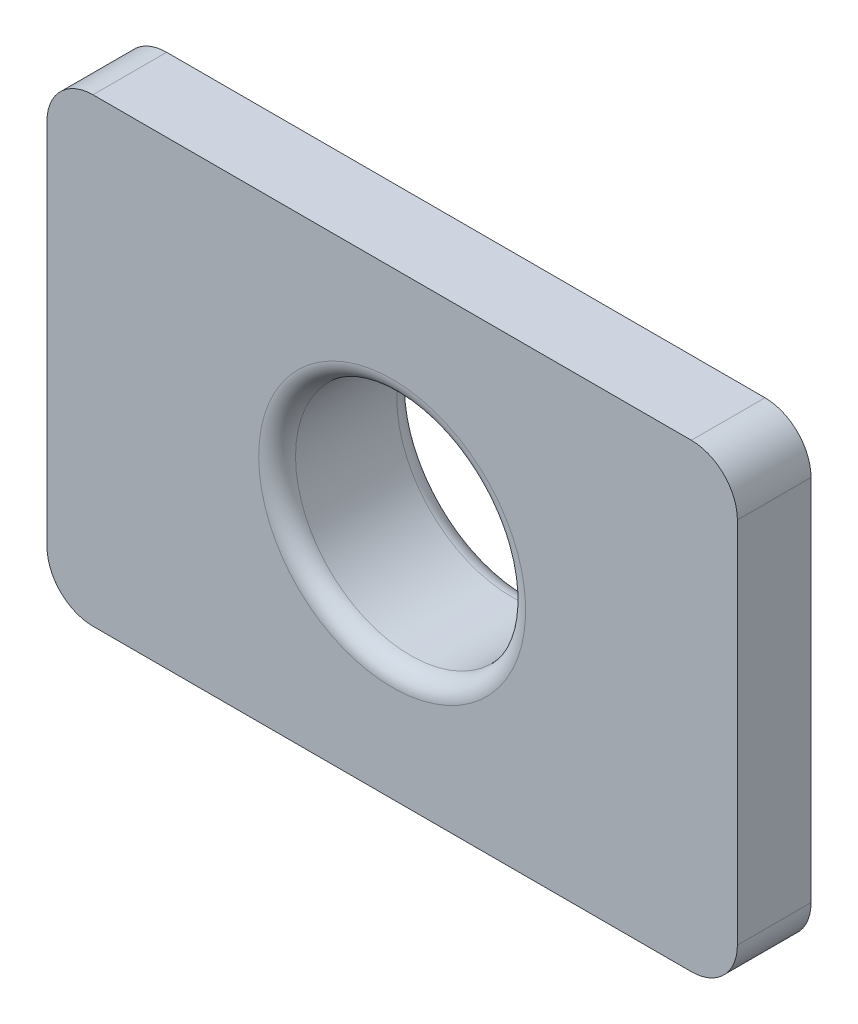
SolidWorks part; units mm, degrees
ref_plane "Front Plane" through (0, 0, 0) normal (0, 0, 1) x (1, 0, 0)
ref_plane "Top Plane" through (0, 0, 0) normal (0, 1, 0) x (1, 0, 0)
ref_plane "Right Plane" through (0, 0, 0) normal (1, 0, 0) x (0, 0, -1)
sketch "Sketch1" plane through (0, 0, 0) normal (0, 0, 1) x (1, 0, 0)
  line L0 (0, 5) -> (15, 5) construction
  line L1 (0, 0) -> (15, 0)
  line L2 (0, 0) -> (0, 10)
  line L3 (0, 10) -> (15, 10)
  line L4 (15, 0) -> (15, 10)
  circle A0 centre (7.5, 5) radius 2.5
  dimension "D3" = 5
  dimension "D1" = 15
  dimension "D2" = 10
extrude "Boss-Extrude1" add sketch "Sketch1" along normal blind 1.6
sketch "Sketch2" plane through (0, 0, 0) normal (0, 0, -1) x (-1, 0, 0)
  line L0 (-15, 5) -> (0, 5) construction
  line L1 (-15, 0) -> (-15, 10) construction
  line L2 (0, 10) -> (0, 0) construction
  circle A0 centre (-7.5, 5) radius 2.5
  circle A1 centre (-7.5, 5) radius 3.5
  dimension "D1" = 7
extrude "Boss-Extrude2" add sketch "Sketch2" along normal blind 1.4
fillet "Fillet3" radius 0.4 4 edges at (4, 5, -1.4) (5, 5, -1.4) (10, 5, 1.6) (4, 5, 0)
fillet "Fillet4" radius 1 4 edges at (15, 10, 0.8) (15, 0, 0.8) (0, 10, 0.8) (0, 0, 0.8)
